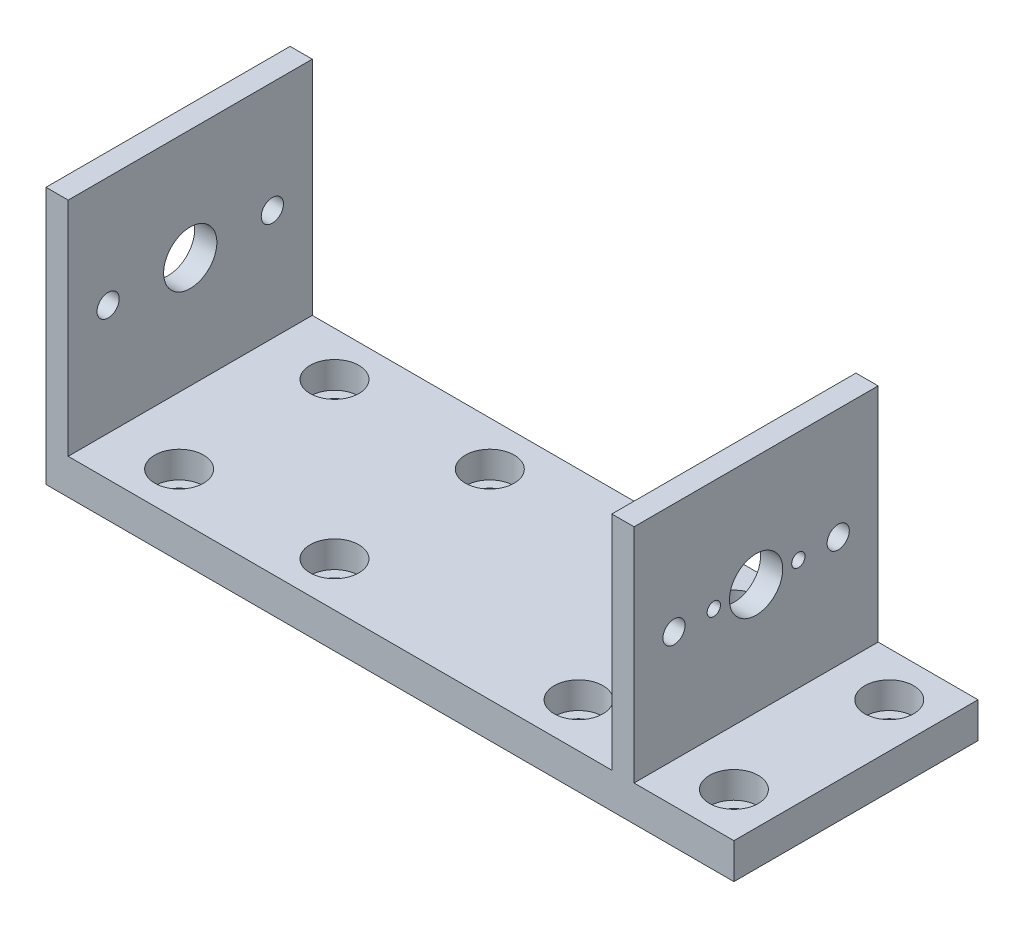
SolidWorks part; units mm, degrees
ref_plane "Front Plane" through (0, 0, 0) normal (0, 0, 1) x (1, 0, 0)
ref_plane "Top Plane" through (0, 0, 0) normal (0, 1, 0) x (1, 0, 0)
ref_plane "Right Plane" through (0, 0, 0) normal (1, 0, 0) x (0, 0, -1)
sketch "Sketch1" plane through (0, 0, 0) normal (0, 1, 0) x (1, 0, 0)
  line L0 (0, 14.013) -> (0, -13.1268) construction
  line L1 (-3.8771, 0) -> (4.5418, 0) construction
  line L2 (-45, 17.5) -> (-45, -17.5) construction
  line L3 (72.5, 27.5) -> (-72.5, 27.5)
  line L4 (-72.5, 27.5) -> (-72.5, -27.5)
  line L5 (72.5, -27.5) -> (-72.5, -27.5)
  line L6 (72.5, 27.5) -> (72.5, -27.5)
  circle A0 centre (-45, 0) radius 10 construction
  circle A1 centre (-62.5, 17.5) radius 3.25
  circle A2 centre (-62.5, -17.5) radius 3.25
  circle A3 centre (-27.5, -17.5) radius 3.25
  circle A4 centre (-27.5, 17.5) radius 3.25
  circle A5 centre (62.5, -17.5) radius 3.25
  circle A6 centre (27.5, -17.5) radius 3.25
  circle A7 centre (27.5, 17.5) radius 3.25
  circle A8 centre (45, 0) radius 10 construction
  circle A9 centre (62.5, 17.5) radius 3.25
  circle A10 centre (-62.5, 17.5) radius 5.5 construction
  circle A11 centre (-27.5, 17.5) radius 5.5 construction
  circle A12 centre (-27.5, -17.5) radius 5.5 construction
  circle A13 centre (-62.5, -17.5) radius 5.5 construction
  circle A14 centre (27.5, -17.5) radius 5.5 construction
  circle A15 centre (27.5, 17.5) radius 5.5 construction
  circle A16 centre (62.5, 17.5) radius 5.5 construction
  circle A17 centre (62.5, -17.5) radius 5.5 construction
  point P19 (-72.5, 0)
  point P33 (0, -27.5)
  point P34 (0, 27.5)
  dimension "D1" = 20
  dimension "D2" = 6.5
  dimension "D10" = 11
  dimension "D3" = 35
  dimension "D4" = 35
  dimension "D5" = 90
  dimension "D6" = 10
  dimension "D7" = 10
  dimension "D8" = 55
  dimension "D9" = 145
extrude "Boss-Extrude1" add sketch "Sketch1" along normal blind 8
sketch "Sketch5" plane through (0, 8, 0) normal (0, 1, 0) x (1, 0, 0)
  circle A0 centre (-62.5, 17.5) radius 5.5
  circle A1 centre (-27.5, 17.5) radius 5.5
  circle A2 centre (27.5, 17.5) radius 5.5
  circle A3 centre (62.5, 17.5) radius 5.5
  circle A4 centre (62.5, -17.5) radius 5.5
  circle A5 centre (27.5, -17.5) radius 5.5
  circle A6 centre (-27.5, -17.5) radius 5.5
  circle A7 centre (-62.5, -17.5) radius 5.5
  dimension "D1" = 11
extrude "Cut-Extrude1" cut sketch "Sketch5" against normal blind 6
sketch "Sketch3" plane through (-72.5, 0, 0) normal (-1, 0, 0) x (0, 0, 1)
  line L0 (-27.5, 0) -> (-27.5, 8)
  line L1 (-27.5, 8) -> (27.5, 8) construction
  line L2 (-27.5, 8) -> (27.5, 8)
  line L3 (27.5, 8) -> (27.5, 0)
  line L4 (27.5, 0) -> (-27.5, 0)
extrude "Boss-Extrude3" add sketch "Sketch3" along normal blind 10
sketch "Sketch4" plane through (0, 8, 0) normal (0, 1, 0) x (1, 0, 0)
  line L0 (-82.5, 27.5) -> (-82.5, -27.5)
  line L1 (-82.5, -27.5) -> (-77.5, -27.5)
  line L2 (-82.5, -27.5) -> (72.5, -27.5) construction
  line L3 (-77.5, -27.5) -> (-77.5, 27.5)
  line L4 (72.5, 27.5) -> (-82.5, 27.5) construction
  line L5 (-77.5, 27.5) -> (-82.5, 27.5)
  line L6 (47.5, 27.5) -> (47.5, -27.5) construction
  line L11 (72.5, -27.5) -> (72.5, 27.5) construction
  line L12 (50, 27.5) -> (45, 27.5)
  line L13 (45, 27.5) -> (45, -27.5)
  line L14 (45, -27.5) -> (50, -27.5)
  line L15 (50, 27.5) -> (50, -27.5)
  dimension "D1" = 5
  dimension "D2" = 25
  dimension "D3" = 5
extrude "Boss-Extrude4" add sketch "Sketch4" along normal blind 50
sketch "Sketch6" plane through (-82.5, 0, 0) normal (-1, 0, 0) x (0, 0, 1)
  line L0 (-27.5, 8) -> (27.5, 8) construction
  line L1 (-27.5, 58) -> (-27.5, 0) construction
  line L2 (27.5, 0) -> (27.5, 58) construction
  line L3 (-27.5, 0) -> (27.5, 0) construction
  line L4 (0, 58) -> (0, 8) construction
  line L5 (-27.5, 58) -> (27.5, 58) construction
  line L6 (0, 33) -> (-27.5, 33) construction
  line L7 (0, 33) -> (27.5, 33) construction
  circle A0 centre (0, 33) radius 6
  circle A1 centre (-18.5, 33) radius 2.5
  circle A2 centre (18.5, 33) radius 2.5
  dimension "D2" = 12
  dimension "D3" = 5
  dimension "D1" = 8
  dimension "D4" = 37
extrude "Cut-Extrude2" cut sketch "Sketch6" against normal through all both and the other way through all
sketch "Sketch8" plane through (50, 0, 0) normal (1, 0, 0) x (0, 0, -1)
  line L0 (-9.525, 33) -> (9.525, 33) construction
  circle A0 centre (0, 33) radius 9.525 construction
  circle A1 centre (9.525, 33) radius 1.5
  circle A2 centre (-9.525, 33) radius 1.5
  dimension "D1" = 19.05
  dimension "D2" = 3
extrude "Cut-Extrude3" cut sketch "Sketch8" against normal blind 10
